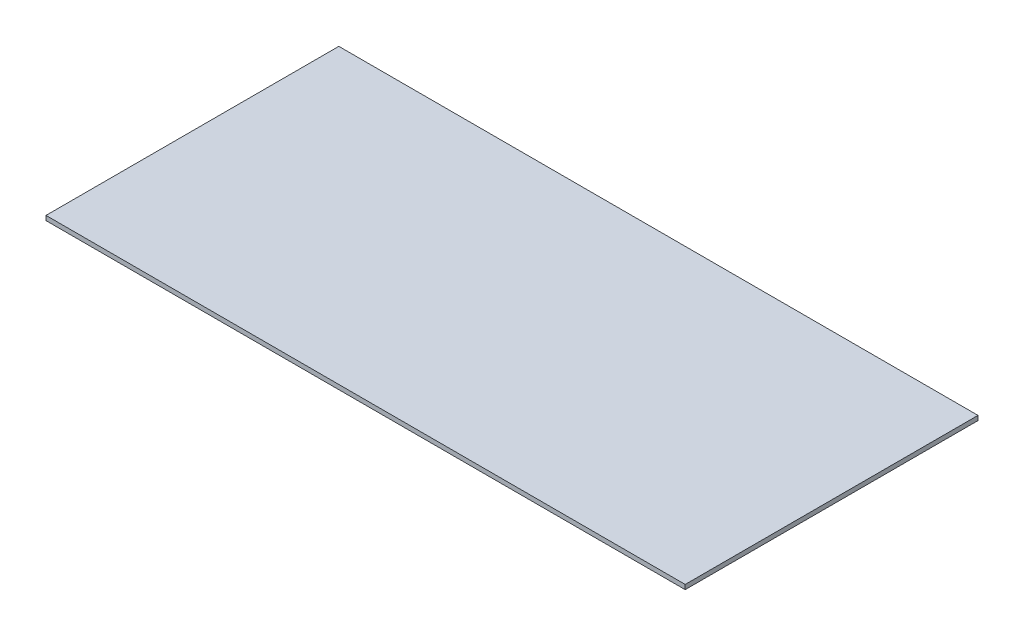
SolidWorks part; units mm, degrees
material "Mahogany"
ref_plane "Front Plane" through (0, 0, 0) normal (0, 0, 1) x (1, 0, 0)
ref_plane "Top Plane" through (0, 0, 0) normal (0, 1, 0) x (1, 0, 0)
ref_plane "Right Plane" through (0, 0, 0) normal (1, 0, 0) x (0, 0, -1)
sketch "Sketch1" plane through (0, 0, 0) normal (0, 1, 0) x (1, 0, 0)
  line L1 (895, -410) -> (-895, -410)
  line L2 (895, -410) -> (895, 410)
  line L3 (895, 410) -> (-895, 410)
  line L4 (-895, -410) -> (-895, 410)
  line L5 (895, -410) -> (-895, 410) construction
  line L6 (895, 410) -> (-895, -410) construction
  point P0 (0, 0)
  dimension "D1" = 1790
  dimension "D2" = 820
extrude "Boss-Extrude1" add sketch "Sketch1" along normal blind 12.7
equation "\"W\"= 1750"
equation "\"L\"= 780"
equation "\"H\"= 780"
equation "\"ARM_BOLT_SPACING\"= 166"
equation "\"ARM_TO_WALL\"= 200"
equation "\"D1@Sketch1\"=\"W\"+40"
equation "\"D2@Sketch1\"=\"L\"+40"
